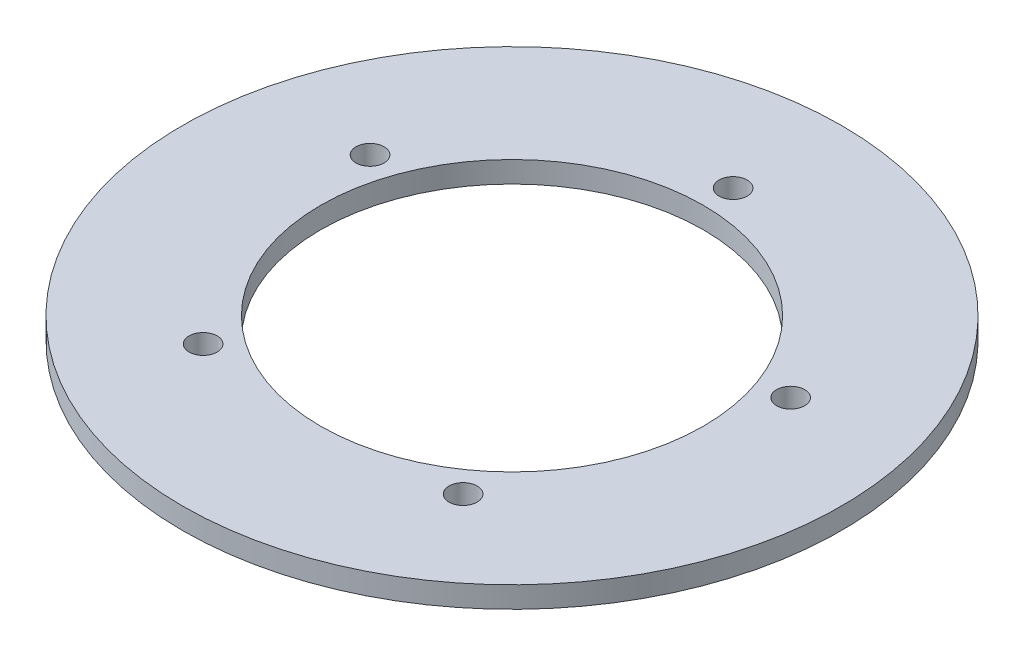
SolidWorks part; units mm, degrees
ref_plane "Front Plane" through (0, 0, 0) normal (0, 0, 1) x (1, 0, 0)
ref_plane "Top Plane" through (0, 0, 0) normal (0, 1, 0) x (1, 0, 0)
ref_plane "Right Plane" through (0, 0, 0) normal (1, 0, 0) x (0, 0, -1)
sketch "Sketch1" plane through (0, 0, 0) normal (0, 1, 0) x (1, 0, 0)
  circle A0 centre (0, 0) radius 77.5
  circle A1 centre (0, 0) radius 45
  dimension "D1" = 155
  dimension "D2" = 90
extrude "Body" add sketch "Sketch1" along normal blind 5
hole_wizard "M6 Clearance Hole1" positions "Sketch2" profile "Sketch3" hole size "M6" standard "ANSI Metric" end condition through all
sketch "Sketch2" plane through (0, 5, 0) normal (0, 1, 0) x (1, 0, 0)
  point P0 (0, 52)
  point P10 (49.4549, 16.0689)
  point P11 (30.5648, -42.0689)
  point P12 (-30.5648, -42.0689)
  point P13 (-49.4549, 16.0689)
  point P15 (0, 0)
  point P19 (0, 0)
  dimension "D1" = 52
  dimension "D3" = 5
sketch "Sketch3" plane through (0, 5, -52) normal (1, 0, 0) x (0, 0, 1)
  line L0 (0, 0) -> (0, 5)
  line L1 (0, 5) -> (3.3, 5)
  line L2 (3.3, 5) -> (3.3, 0)
  line L5 (3.3, 0) -> (0, 0)
  line L11 (0, -6.35) -> (0, 107.95) construction
  dimension "Thru Hole Dia." = 6.6
  dimension "Thru Hole Depth" = 5
